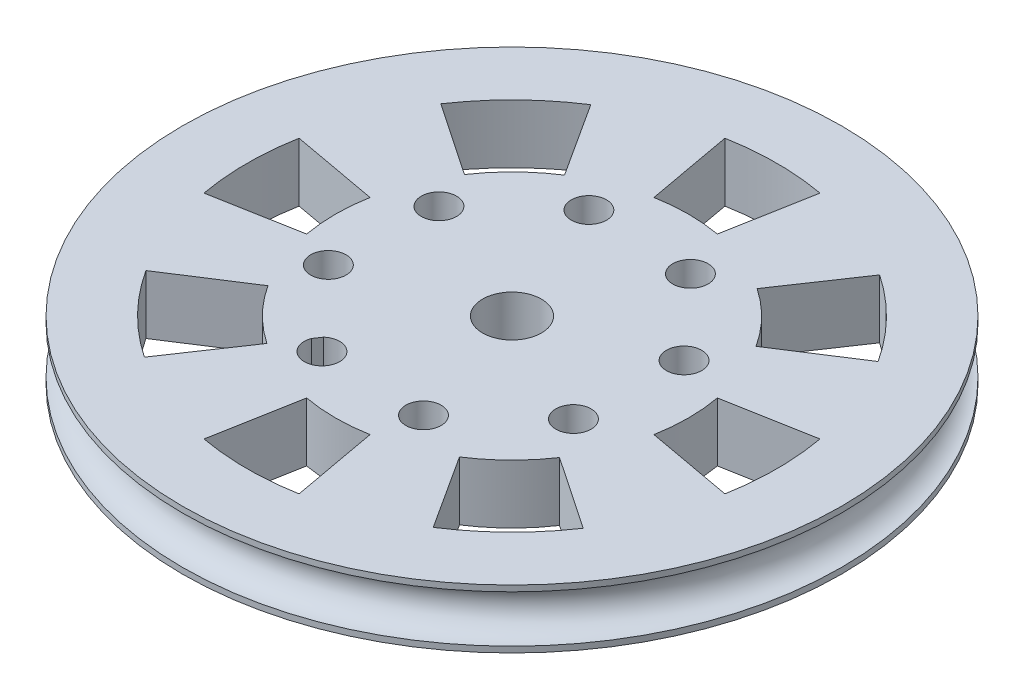
SolidWorks part; units mm, degrees
ref_plane "Front Plane" through (0, 0, 0) normal (0, 0, 1) x (1, 0, 0)
ref_plane "Top Plane" through (0, 0, 0) normal (0, 1, 0) x (1, 0, 0)
ref_plane "Right Plane" through (0, 0, 0) normal (1, 0, 0) x (0, 0, -1)
sketch "Sketch6" plane through (0, 0, 0) normal (0, 1, 0) x (1, 0, 0)
  circle A0 centre (0, 0) radius 28
  dimension "D1" = 56
extrude "Boss-Extrude3" add sketch "Sketch6" along normal blind 5
sketch "Sketch7" plane through (0, 5, 0) normal (0, 1, 0) x (1, 0, 0)
  line L0 (22.1342, 4.0409) -> (12.0756, 4.0409)
  line L1 (0, 0) -> (18.9009, 12.2068)
  line L2 (-22.1342, -4.0409) -> (-13.0625, -4.0409)
  line L3 (0, 0) -> (12.5929, 18.6459)
  line L4 (-18.9009, -12.2068) -> (-12.0226, -5.4686)
  line L5 (0, 0) -> (4.0409, 22.1342)
  line L6 (-4.0409, 22.1342) -> (-4.0409, 12.4855)
  line L7 (0, 0) -> (-4.0409, 22.1342)
  line L8 (4.0409, 22.1342) -> (4.0409, 12.1198)
  line L9 (0, 0) -> (-12.2068, 18.9009)
  line L10 (18.9009, 12.2068) -> (11.6421, 5.0957)
  line L11 (0, 0) -> (-18.6459, 12.5929)
  line L12 (0, 0) -> (-22.1342, 4.0409)
  line L13 (0, 0) -> (-22.1342, -4.0409)
  line L14 (-12.2068, 18.9009) -> (-5.5841, 12.1405)
  line L15 (0, 0) -> (-18.9009, -12.2068)
  line L16 (12.2068, -18.9009) -> (4.9776, -11.5215)
  line L17 (0, 0) -> (-12.5929, -18.6459)
  line L18 (0, 0) -> (-4.0409, -22.1342)
  line L19 (0, 0) -> (4.0409, -22.1342)
  line L20 (0, 0) -> (12.2068, -18.9009)
  line L21 (0, 0) -> (18.6459, -12.5929)
  line L22 (0, 0) -> (22.1342, -4.0409)
  line L23 (0, 0) -> (22.1342, 4.0409)
  line L24 (-0.4934, 0) -> (8.2772, 21.1742) construction
  line L25 (-4.0409, 9.6525) -> (-4.0409, -10.2073)
  line L26 (-3.4847, 9.9975) -> (9.7679, -3.5305)
  line L27 (4.0409, 9.2489) -> (4.0409, -9.6525)
  line L28 (5.5426, 11.7391) -> (12.5929, 18.6459)
  line L29 (9.4991, 2.9964) -> (-4.0262, -10.2536)
  line L30 (9.0756, 4.0409) -> (-9.9998, 4.0409)
  line L31 (11.3688, -4.0409) -> (22.1342, -4.0409)
  line L32 (11.621, -5.4221) -> (18.6459, -12.5929)
  line L33 (3.1245, -9.6299) -> (-10.1281, 3.8981)
  line L34 (4.0409, -12.4855) -> (4.0409, -22.1342)
  line L35 (-4.0409, -11.1613) -> (-4.0409, -22.1342)
  line L36 (-5.9232, -12.112) -> (-12.5929, -18.6459)
  line L37 (-10.1256, -3.6102) -> (3.3997, 9.6398)
  line L38 (-10.0625, -4.0409) -> (9.013, -4.0409)
  line L39 (-12.3557, 4.0409) -> (-22.1342, 4.0409)
  line L40 (-12.2275, 6.0411) -> (-18.6459, 12.5929)
  circle A0 centre (0, 0) radius 22.5
  circle A1 centre (0, 0) radius 15
  arc A2 (-4.9545, 9.6291) -> (-9.6826, 4.8489) centre (0, 0) ccw
  circle A3 centre (4.4762, 10.6843) radius 1.5
  circle A4 centre (10.5756, 4.0409) radius 1.5
  circle A5 centre (10.1909, -4.9696) radius 1.5
  circle A6 centre (3.5475, -11.069) radius 1.5
  circle A7 centre (-5.4631, -10.6843) radius 1.5
  circle A8 centre (-11.5625, -4.0409) radius 1.5
  circle A9 centre (-11.1778, 4.9696) radius 1.5
  circle A10 centre (-4.5344, 11.069) radius 1.5
  arc A11 (3.0025, 10.4043) -> (-3.2247, 10.3376) centre (0, 0) ccw
  arc A12 (9.5392, 5.1253) -> (5.3102, 9.4376) centre (0, 0) ccw
  arc A13 (10.2575, -3.4711) -> (10.5264, 2.5417) centre (0, 0) ccw
  arc A14 (4.4512, -9.8718) -> (9.0512, -5.9449) centre (0, 0) ccw
  arc A15 (-4.1211, -10.0141) -> (2.1162, -10.6201) centre (0, 0) ccw
  arc A16 (-10.063, -4.0002) -> (-5.7054, -9.204) centre (0, 0) ccw
  arc A17 (-10.0866, 3.9404) -> (-10.3641, -3.1388) centre (0, 0) ccw
  dimension "D1" = 12
  dimension "D2" = 8
  dimension "D3" = 3
  dimension "D4" = 30
  dimension "D5" = 45
extrude "Cut-Extrude4" cut sketch "Sketch7" against normal through all both and the other way through all contours A1 L1 A0 L3 | A1 L5 A0 L7 | A1 L9 A0 L11 | A1 L12 A0 L13 | A1 L15 A0 L17 | A1 L18 A0 L19 | A1 L20 A0 L21 | A1 L22 A0 L23 region at (18.8969, 5, 0) region at (13.4806, 5, -13.2062) region at (13.2062, 5, 13.4806) region at (0, 5, -18.8969) region at (0, 5, 18.8969) region at (-13.2062, 5, -13.4806) region at (-13.4806, 5, 13.2062) region at (-18.8969, 5, 0)
extrude "Cut-Extrude5" cut sketch "Sketch7<8>" against normal through all both and the other way through all contours A10 | A4 | A5 | A6 | A7 | A8 | A9 | L24 A3 | A3 L24 region at (10.5756, 5, -4.0409) region at (10.1909, 5, 4.9696) region at (4.823, 5, -10.5407) region at (3.6302, 5, -11.0348) region at (3.5475, 5, 11.069) region at (-4.5344, 5, -11.069) region at (-5.4589, 5, 10.6871) region at (-11.1778, 5, -4.9696) region at (-11.5625, 5, 4.0409)
sketch "Sketch7<8>" plane through (0, 5, 0) normal (0, 1, 0) x (1, 0, 0) same geometry as "Sketch7"
sketch "Sketch10" plane through (0, 0, 0) normal (0, 0, 1) x (1, 0, 0)
  line L0 (28, 0) -> (28, 5) construction
  circle A0 centre (28, 2.5) radius 2
  dimension "D1" = 4
ref_axis "Axis1" through (0, 40.6143, 0) along (0, -1, 0)
revolve "Cut-Revolve1" cut sketch "Sketch10" angle 360 about axis through (0, 40.6143, 0) along (0, -1, 0)
sketch "Sketch11" plane through (0, 0, 0) normal (0, 1, 0) x (1, 0, 0)
  circle A0 centre (0, 0) radius 2.5
  dimension "D1" = 5
extrude "Cut-Extrude14" cut sketch "Sketch11" against normal blind 5 and the other way through all
sketch "Sketch12" plane through (0, 0, 0) normal (0, 1, 0) x (1, 0, 0)
  line L1 (0, 7) -> (-6.0622, 3.5)
  line L2 (-6.0622, 3.5) -> (-6.0622, -3.5)
  line L3 (-6.0622, -3.5) -> (0, -7)
  line L4 (0, -7) -> (6.0622, -3.5)
  line L5 (6.0622, -3.5) -> (6.0622, 3.5)
  line L6 (6.0622, 3.5) -> (0, 7)
  circle A0 centre (0, 0) radius 9
  circle A1 centre (0, 0) radius 6.0622 construction
  dimension "D2" = 18
  dimension "D1" = 7
extrude "Boss-Extrude4" add sketch "Sketch12" against normal blind 4
